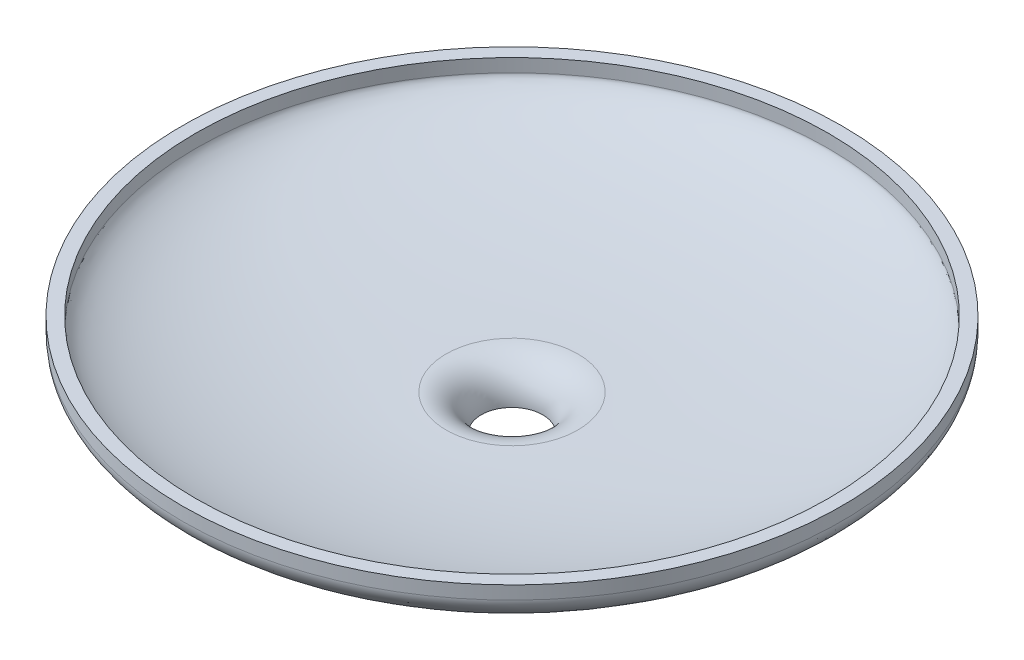
SolidWorks part; units mm, degrees
ref_plane "Front Plane" through (0, 0, 0) normal (0, 0, 1) x (1, 0, 0)
ref_plane "Top Plane" through (0, 0, 0) normal (0, 1, 0) x (1, 0, 0)
ref_plane "Right Plane" through (0, 0, 0) normal (1, 0, 0) x (0, 0, -1)
sketch "Sketch2" plane through (0, 0, 0) normal (0, 0, 1) x (1, 0, 0)
  line L0 (-72, 23) -> (-72, 20)
  line L1 (-75, 23) -> (-75, 20)
  line L2 (0, 0) -> (0, 18449.246) construction
  line L3 (-10, 0) -> (-7, 0)
  line L4 (-75, 23) -> (-72, 23)
  arc A0 (-10, 0) -> (-15, 5) centre (-15, 0) ccw
  arc A1 (-7, 0) -> (-15, 8) centre (-15, 0) ccw
  ellipse E0 centre (-15, 20) end of major axis (45, 20) minor radius 15 (-15, 5) -> (-75, 20) cw
  spline S0 degree 1 poles (-15, 8) (-72, 20) knots 0 0 1 1 construction
  spline S1 degree 3 poles (-72, 20) (-72, 19.9472) (-71.9913, 19.854) (-71.9157, 19.5753) (-71.6006, 18.9932) (-70.6163, 17.9843) (-68.4413, 16.4512) (-64.1857, 14.4402) (-56.9862, 12.2432) (-48.0623, 10.41) (-37.8043, 9.0385) (-28.4945, 8.3323) (-20.8182, 8.0476) (-16.9359, 8) (-15, 8) knots 3.141593 3.141593 3.141593 3.141593 3.19068 3.239767 3.337942 3.436117 3.534292 3.730641 3.926991 4.12334 4.31969 4.516039 4.614214 4.712389 4.712389 4.712389 4.712389
  dimension "D2" = 5
  dimension "D1" = 10
  dimension "D3" = 15
  dimension "D4" = 60
  dimension "D5" = 3
  dimension "D6" = 3
revolve "Revolve1" add sketch "Sketch2" angle 360 about L2
